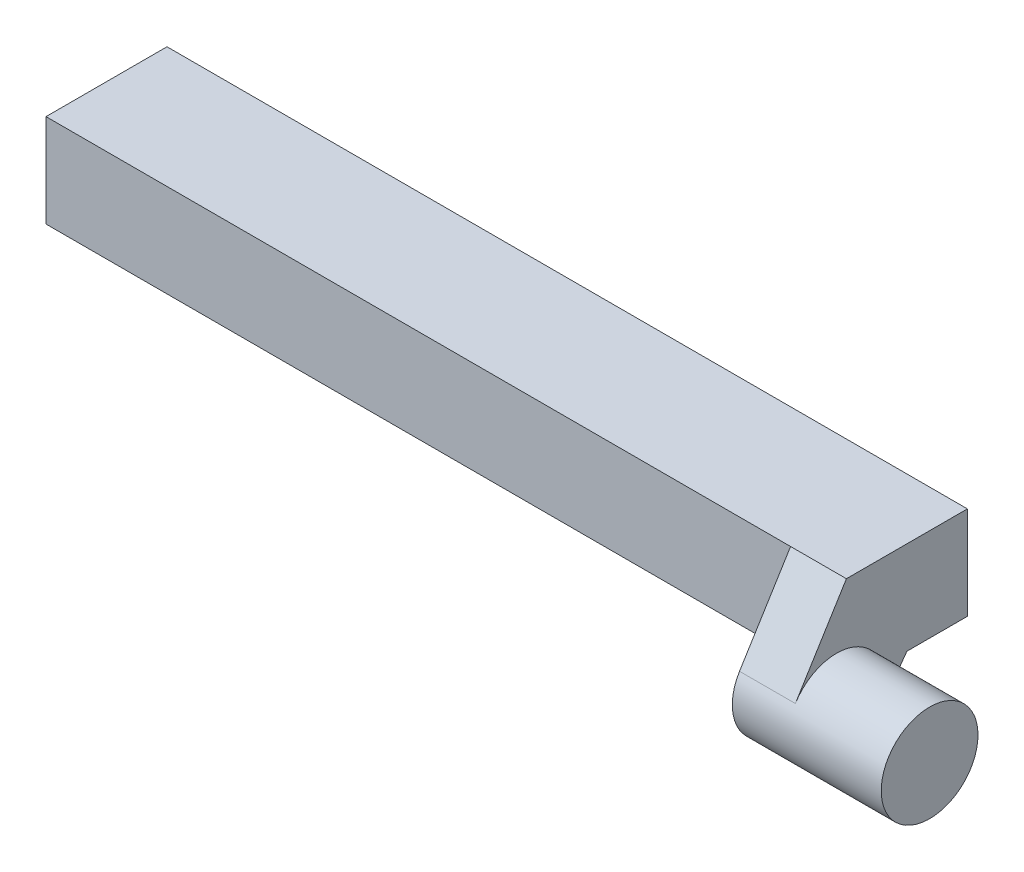
SolidWorks part; units mm, degrees
ref_plane "Front Plane" through (0, 0, 0) normal (0, 0, 1) x (1, 0, 0)
ref_plane "Top Plane" through (0, 0, 0) normal (0, 1, 0) x (1, 0, 0)
ref_plane "Right Plane" through (0, 0, 0) normal (1, 0, 0) x (0, 0, -1)
sketch "Sketch2" plane through (0, 0, 0) normal (1, 0, 0) x (0, 0, -1)
  line L1 (-2.25, -2.25) -> (2.25, -2.25)
  line L2 (-2.25, -2.25) -> (-2.25, 2.25)
  line L3 (-2.25, 2.25) -> (2.25, 2.25)
  line L4 (2.25, -2.25) -> (2.25, 2.25)
  line L5 (-2.25, -2.25) -> (2.25, 2.25) construction
  line L6 (-2.25, 2.25) -> (2.25, -2.25) construction
  line L7 (3.25, -2.5) -> (-3.25, -2.5)
  line L8 (3.25, -2.5) -> (3.25, 2.5)
  line L9 (3.25, 2.5) -> (-3.25, 2.5)
  line L10 (-3.25, -2.5) -> (-3.25, 2.5)
  line L11 (3.25, -2.5) -> (-3.25, 2.5) construction
  line L12 (3.25, 2.5) -> (-3.25, -2.5) construction
  point P0 (0, 0)
  point P5 (0, 0)
  dimension "D1" = 4.5
  dimension "D2" = 4.5
  dimension "D3" = 6.5
  dimension "D4" = 5
extrude "Boss-Extrude1" add sketch "Sketch2" along normal blind 10
extrude "Boss-Extrude2" add sketch "Sketch2<2>" along normal blind 30 from surface contours L1 L4 L3 L2 | L10 L7 L8 L9 L4 L1 L2 L3 region at (0, 0, 0) region at (0, -2.418, 0) starting at face at (10, 0, 0)
sketch "Sketch2<2>" plane through (0, 0, 0) normal (1, 0, 0) x (0, 0, -1) same geometry as "Sketch2"
sketch "Sketch5" plane through (40, 0, 0) normal (1, 0, 0) x (0, 0, -1)
  line L0 (-0.02, -0.4959) -> (-4.75, -0.4959) construction
  line L5 (-5.9921, -1.9359) -> (-3.25, 2.5)
  line L6 (-3.25, 2.5) -> (3.25, 2.5)
  line L7 (3.25, 2.5) -> (3.25, -2.5)
  line L8 (3.25, -2.5) -> (0, -2.5)
  line L9 (-3.25, -2.5) -> (3.25, -2.5) construction
  line L10 (0, -2.5) -> (-1.67, -4.8214)
  arc A1 (-5.9921, -1.9359) -> (-1.67, -4.8214) centre (-3.7806, -3.303) ccw
  dimension "D2" = 2.6
  dimension "D1" = 4.73
extrude "Boss-Extrude3" add sketch "Sketch5" along normal blind 3
sketch "Sketch6" plane through (43, 0, 0) normal (1, 0, 0) x (0, 0, -1)
  circle A1 centre (-3.7806, -3.303) radius 2.6
  dimension "D1" = 5.2
extrude "Boss-Extrude4" add sketch "Sketch6" along normal blind 5
